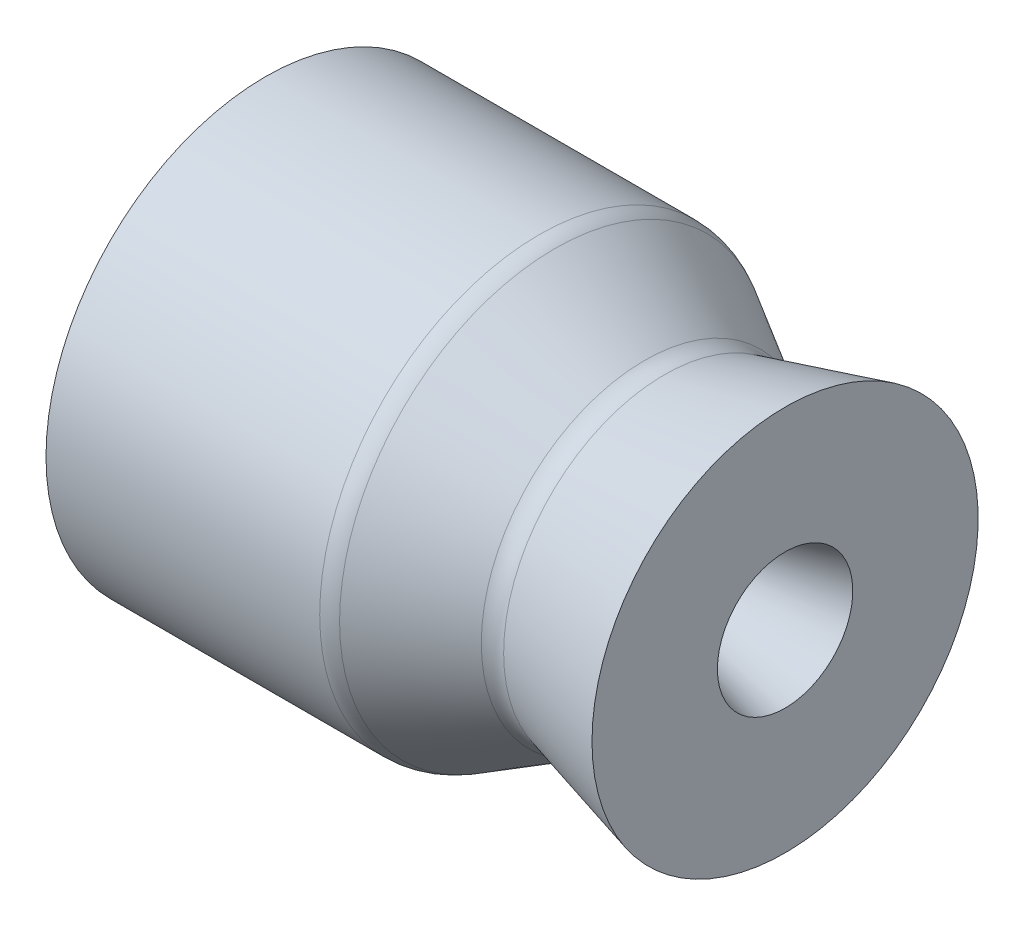
SolidWorks part; units mm, degrees
material "AISI 304"
ref_plane "Front Plane" through (0, 0, 0) normal (0, 0, 1) x (1, 0, 0)
ref_plane "Top Plane" through (0, 0, 0) normal (0, 1, 0) x (1, 0, 0)
ref_plane "Right Plane" through (0, 0, 0) normal (1, 0, 0) x (0, 0, -1)
sketch "chamberNozzle" plane through (0, 0, 0) normal (0, 0, 1) x (1, 0, 0)
  line L0 (0, 0) -> (366.3783, 0) construction
  line L1 (0, 0) -> (0, 38.1) construction
  line L2 (0, 38.1) -> (110.897, 38.1)
  line L3 (158.9188, 24.511) -> (158.9188, 13.97) construction
  line L4 (117.247, 36.3985) -> (153.6483, 15.3822)
  line L5 (150.9294, 13.97) -> (106.9103, 13.97) construction
  line L6 (161.647, 14.3292) -> (210.5452, 27.4314)
  line L7 (210.5452, 27.4314) -> (210.5452, 0) construction
  line L8 (0, 88.9) -> (110.897, 88.9)
  line L9 (117.247, 87.1985) -> (153.6483, 66.1822)
  line L10 (161.647, 65.1292) -> (210.5452, 78.2314)
  line L11 (0, 38.1) -> (0, 45.72)
  line L12 (0, 45.72) -> (5.08, 45.72)
  line L13 (5.08, 45.72) -> (5.08, 55.88)
  line L14 (5.08, 55.88) -> (0, 55.88)
  line L15 (0, 55.88) -> (0, 88.9)
  line L17 (210.5452, 78.2314) -> (210.5452, 27.4314)
  arc A0 (153.6483, 15.3822) -> (161.647, 14.3292) centre (158.9188, 24.511) ccw
  arc A1 (110.897, 38.1) -> (117.247, 36.3985) centre (110.897, 25.4) cw
  arc A2 (153.6483, 66.1822) -> (161.647, 65.1292) centre (158.9188, 75.311) ccw
  arc A3 (110.897, 88.9) -> (117.247, 87.1985) centre (110.897, 76.2) cw
  point P16 (114.3, 38.1)
  point P28 (5.08, 50.8)
  dimension "D4" = 21.082
  dimension "D9" = 12.7
  dimension "D1" = 38.1
  dimension "D3" = 13.97
  dimension "D5" = 30
  dimension "D6" = 15
  dimension "D10" = 50.8
  dimension "D11" = 10.16
  dimension "D12" = 5.08
  dimension "D13" = 12.7
revolve "Revolve1" add sketch "chamberNozzle" angle 360 about L0
ref_plane "chamberInterface" through (0, 0, 0) normal (-1, 0, 0) x (0, 0, 1)
sketch "Sketch1" plane through (0, 0, 0) normal (-1, 0, 0) x (0, 0, 1)
  line L0 (0, 55.88) -> (0, 88.9) construction
  circle A0 centre (0, 0) radius 72.39 construction
  circle A1 centre (0, 0) radius 55.88 construction
  circle A2 centre (0, 0) radius 88.9 construction
  point P10 (0, 72.39)
hole_wizard "1/2 (0.5) Diameter Hole1" positions "Sketch2" profile "Sketch3" hole size "1/2" standard "ANSI Inch"
sketch "Sketch2" plane through (0, 0, 0) normal (-1, 0, 0) x (0, 0, 1)
  circle A0 centre (0, 0) radius 72.39 construction
  point P0 (-72.39, 0)
sketch "Sketch3" plane through (0, 0, -72.39) normal (0, 1, 0) x (0, 0, 1)
  line L0 (0, 0) -> (0, 16.5155)
  line L1 (0, 16.5155) -> (6.35, 12.7)
  line L2 (6.35, 12.7) -> (6.35, 0.635)
  line L3 (6.35, 0.635) -> (6.985, 0)
  line L5 (6.985, 0) -> (0, 0)
  line L6 (-6.35, 0.635) -> (-6.985, 0) construction
  line L10 (0, 16.5155) -> (-6.35, 12.7) construction
  line L11 (0, -6.35) -> (0, 107.95) construction
  dimension "Hole Dia." = 12.7
  dimension "Hole Depth" = 12.7
  dimension "Near C'Sink Dia." = 13.97
  dimension "Near C'Sink Angle" = 90
  dimension "Drill Angle" = 118
pattern_circular "CirPattern1" count 5 over 360 about axis through (0, 0, 0) along (-1, 0, 0) of "1/2 (0.5) Diameter Hole1"
equation "\"l_star\"= .8m'characteristic length"
equation "\"R_t\"= .55in'throat radius"
equation "\"V_c\"= \"l_star\" * \"R_t\"'chamber volume"
equation "\"D_c\"= 3in'chamber diameter"
equation "\"L_c\"= \"V_c\" / ( ( pi * \"D_c\" ) / 4 )'chamber length"
equation "\"eps_x\"= 3.8557'expansion ratio"
equation "\"D_e\"= \"R_t\" * 2 * sqr ( \"eps_x\" )'exit diameter"
equation "\"arc_t\"= 1.5in * \"R_t\"'arc between convergent and divergent"
equation "\"D3@chamberNozzle\" = \"R_t\""
equation "\"D7@chamberNozzle\" = \"D_e\" / 2"
equation "\"D1@chamberNozzle\" = \"D_c\" / 2"
equation "\"D12@chamberNozzle\"=\"D11@chamberNozzle\"/2"
equation "\"D13@chamberNozzle\"=\"D10@chamberNozzle\"/4"
